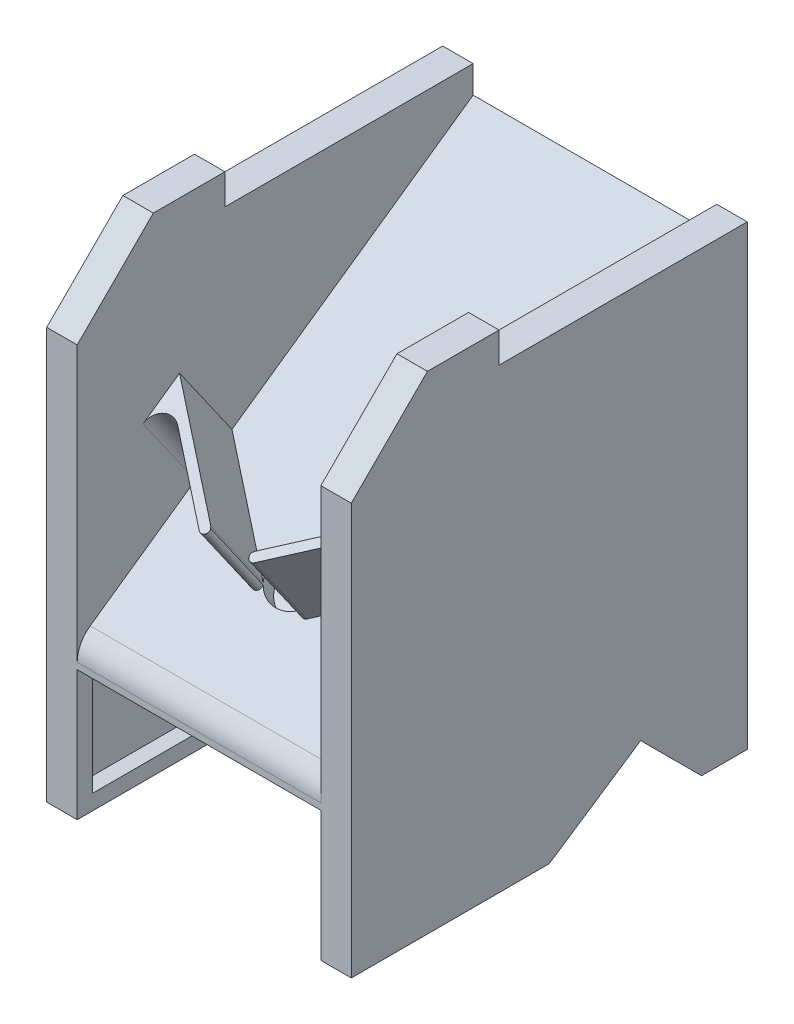
SolidWorks part; units mm, degrees
ref_plane "Front Plane" through (0, 0, 0) normal (0, 0, 1) x (1, 0, 0)
ref_plane "Top Plane" through (0, 0, 0) normal (0, 1, 0) x (1, 0, 0)
ref_plane "Right Plane" through (0, 0, 0) normal (1, 0, 0) x (0, 0, -1)
sketch "Sketch5" plane through (0, 0, 0) normal (0, 1, 0) x (1, 0, 0)
  line L1 (0, 0) -> (100, 0)
  line L2 (0, 0) -> (0, 130)
  line L3 (0, 130) -> (100, 130)
  line L4 (100, 0) -> (100, 130)
  dimension "D1" = 130
  dimension "D2" = 100
extrude "Boss-Extrude1" add sketch "Sketch5" along normal blind 150
sketch "Sketch7" plane through (100, 0, 0) normal (1, 0, 0) x (0, 0, -1)
  line L0 (130, 141.027) -> (0, 50)
  line L1 (115.8456, 131.116) -> (0, 50) construction
  line L2 (0, 150) -> (0, 0) construction
  line L3 (130, 133.7023) -> (0, 42.6754)
  line L4 (119.2871, 126.201) -> (3.4415, 45.0851) construction
  line L5 (130, 150) -> (130, 0) construction
  line L7 (0, 0) -> (130, 0)
  line L8 (130, 0) -> (130, 150)
  line L9 (130, 150) -> (0, 150)
  line L10 (0, 150) -> (0, 0)
  line L11 (0, 0) -> (130, 0)
  line L12 (130, 0) -> (130, 150)
  line L13 (130, 150) -> (0, 150)
  line L14 (0, 150) -> (0, 0)
  line M6 (0, 0) -> (130, 0)
  line M7 (130, 0) -> (130, 150)
  line M8 (130, 150) -> (0, 150)
  line M9 (0, 150) -> (0, 0)
  dimension "D1" = 50
  dimension "D2" = 55
  dimension "D3" = 0
  dimension "D4" = 6
extrude "Cut-Extrude1" cut sketch "Sketch7" against normal mid plane 80 from offset 50 contours L3 M7 M9 M6 | L0 M7 M8 M9 region at (100, 116.4204, -46.9015) region at (100, 48.0093, -76.182) offset against normal yes
ref_plane "Plane2" through (50, 0, 0) normal (-1, 0, 0) x (0, 0, 1)
sketch "Sketch17" plane through (0, 275.4121, -321.9218) normal (0, -0.8192, -0.5736) x (1, 0, 0)
  line L0 (90, 315.183) -> (90, 238.4945) construction
  line L1 (10, 374.2932) -> (90, 374.2932)
  line L2 (10, 374.2932) -> (10, 334.2932)
  line L3 (10, 334.2932) -> (90, 334.2932)
  line L4 (90, 374.2932) -> (90, 334.2932)
  line L6 (10, 315.183) -> (10, 238.4945) construction
  line L8 (10, 234.2932) -> (10, 392.9939) construction
  line L9 (10, 234.2932) -> (90, 234.2932) construction
  dimension "D1" = 40
  dimension "D2" = 100
extrude "Boss-Extrude3" add sketch "Sketch17" against normal blind 5 from offset 30
sketch "Sketch10" plane through (0, 33.5505, 23.4923) normal (0, 0.8192, 0.5736) x (1, 0, 0)
  line L0 (50, 28.6788) -> (50, 172.6872) construction
  line L1 (10, 28.6788) -> (90, 28.6788) construction
  line L2 (100, 86.0365) -> (100, 0) construction
  line L3 (0, 83.1783) -> (100, 83.1783)
  line L4 (0, 83.1783) -> (0, 53.1783)
  line L5 (0, 53.1783) -> (100, 53.1783)
  line L6 (100, 83.1783) -> (100, 53.1783)
  line L7 (0, 83.1783) -> (100, 53.1783) construction
  line L8 (0, 53.1783) -> (100, 83.1783) construction
  line L9 (10, 183.1783) -> (90, 183.1783) construction
  circle A0 centre (50, 68.1783) radius 8.75
  point P4 (50, 68.1783)
  dimension "D1" = 17.5
  dimension "D2" = 30
  dimension "D3" = 100
extrude "Cut-Extrude3" cut sketch "Sketch10" against normal blind 100 contours A0 region at (50, 72.656, -32.3561)
sketch "Sketch18" plane through (0, 0, 0) normal (1, 0, 0) x (0, 0, -1)
  line L0 (130, 150) -> (130, 0) construction
  line L1 (0, 150) -> (48.5, 150)
  line L2 (0, 150) -> (0, 160)
  line L3 (0, 160) -> (48.5, 160)
  line L4 (48.5, 150) -> (48.5, 160)
  dimension "D1" = 81.5
  dimension "D2" = 10
extrude "Boss-Extrude4" add sketch "Sketch18" along normal blind 10
extrude "Boss-Extrude5" add sketch "Sketch18<2>" against normal blind 10 from offset 100
sketch "Sketch18<2>" plane through (0, 0, 0) normal (1, 0, 0) x (0, 0, -1) same geometry as "Sketch18"
sketch "Sketch21" plane through (0, 0, 0) normal (1, 0, 0) x (0, 0, -1)
  line L0 (62.4242, 63.1905) -> (29.6581, 40.2475)
  line L1 (62.4242, 63.1905) -> (51.5263, 78.7544)
  line L2 (29.6581, 40.2475) -> (18.7602, 55.8114)
  line L3 (51.5263, 78.7544) -> (18.7602, 55.8114)
  line L4 (130, 133.7023) -> (0, 42.6754) construction
  line L5 (65.2921, 59.0948) -> (32.526, 36.1517)
  line L6 (65.2921, 59.0948) -> (32.526, 36.1517)
  line L7 (65.2921, 59.0948) -> (69.3071, 53.3607)
  line L8 (32.526, 36.1517) -> (36.541, 30.4177)
  line L9 (69.3071, 53.3607) -> (36.541, 30.4177)
  dimension "D1" = 90
  dimension "D3" = 7
  dimension "D2" = 5
extrude "Cut-Extrude5" cut sketch "Sketch21" along normal blind 70 contours L1 L3 L2 L0 | L9 L7 L5 L8 region at (0, 59.501, -40.5922) region at (0, 44.7562, -50.9166)
fillet "Fillet1" radius 5 2 edges at (5, 30.4177, -36.541) (5, 40.2475, -29.6581)
sketch "Sketch22" plane through (0, 0, 0) normal (-1, 0, 0) x (0, 0, 1)
  line L0 (-115, 0) -> (-95, 20)
  line L1 (-130, 0) -> (0, 0) construction
  line L3 (-95, 20) -> (-65, 0)
  line L4 (-115, 0) -> (-65, 0)
  dimension "D1" = 20
  dimension "D2" = 20
  dimension "D3" = 15
  dimension "D4" = 65
extrude "Cut-Extrude6" cut sketch "Sketch22" against normal blind 120
fillet "Fillet2" radius 10 1 edges at (50, 50, 0)
chamfer "Chamfer2" distance 25 angle 45 2 edges at (95, 160, 0) (5, 160, 0)
sketch "Sketch23" plane through (0, 33.5505, 23.4923) normal (0, 0.8192, 0.5736) x (1, 0, 0)
  line L0 (-11.5431, 68.1783) -> (122.3966, 68.1783) construction
  line L1 (122.3966, 63.1783) -> (-12.5005, 63.1783) construction
  line L3 (50, 51.189) -> (50, 201.2531) construction
  line L4 (57.1807, 63.1783) -> (90, 90.7169)
  line L6 (90, 187.3795) -> (90, 33.8845) construction
  line L7 (42.8193, 63.1783) -> (10, 90.7169)
  line L8 (40.8909, 60.8801) -> (8.0716, 88.4188)
  line L9 (59.1091, 60.8801) -> (91.9284, 88.4188)
  line L10 (10, 90.7169) -> (10, 70.6222)
  line L11 (10, 187.3795) -> (10, 33.8845) construction
  line L12 (90, 90.7169) -> (90, 71.7501)
  arc A0 (59.1091, 60.8801) -> (57.1807, 63.1783) centre (58.1449, 62.0292) cw
  circle A1 centre (50, 68.1783) radius 8.75 construction
  arc A2 (40.8909, 60.8801) -> (42.8193, 63.1783) centre (41.8551, 62.0292) ccw
  point P5 (57.1807, 63.1783)
  point P6 (42.8193, 63.1783)
  circle M9 centre (50, 68.1783) radius 8.75
  line M10 (10, 187.3795) -> (10, 33.8845)
  line M12 (90, 33.8845) -> (90, 187.3795)
  dimension "D1" = 5
  dimension "D2" = 50
  dimension "D3" = 3
  dimension "D4" = 3
extrude "Boss-Extrude6" add sketch "Sketch23" along normal blind 30 contours A0 L9 L4 M12 M9 | L8 A2 L7 M9 M10 region at (73.6181, 76.5869, -37.97) region at (26.3819, 76.5869, -37.97)
fillet "Fillet3" radius 5 2 edges at (10, 95.6246, -39.007) (90, 95.6246, -39.007)
sketch "Sketch24" plane through (10, 0, 0) normal (1, 0, 0) x (0, 0, -1)
  line L0 (26.7902, 44.3432) -> (29.6581, 40.2475)
  line L1 (22.6945, 41.4754) -> (17.5323, 48.8477)
  line L2 (17.5323, 48.8477) -> (5, 40.0725)
  line L3 (5, 40.0725) -> (5, 5)
  line L4 (5, 5) -> (63.4861, 5)
  line L5 (63.4861, 5) -> (95.6371, 26.434)
  line L6 (95.6371, 26.434) -> (117.0711, 5)
  line L7 (117.0711, 5) -> (125, 5)
  line L8 (125, 5) -> (125, 124.0974)
  line L9 (125, 124.0974) -> (58.4899, 77.5265)
  line L10 (58.4899, 77.5265) -> (66.52, 66.0584)
  line L11 (66.52, 66.0584) -> (69.3878, 61.9627)
  line L12 (69.3878, 61.9627) -> (76.2708, 52.1328)
  line L13 (76.2708, 52.1328) -> (43.5047, 29.1898)
  line L14 (29.5774, 31.6455) -> (28.4302, 33.2838)
  line L15 (28.4302, 33.2838) -> (25.5624, 37.3796)
  line L16 (95, 20) -> (115, 0)
  line L17 (115, 0) -> (130, 0)
  line L18 (130, 0) -> (130, 133.7023)
  line L19 (130, 133.7023) -> (51.5263, 78.7544)
  line L20 (51.5263, 78.7544) -> (62.4242, 63.1905)
  line L21 (62.4242, 63.1905) -> (65.2921, 59.0948)
  line L22 (65.2921, 59.0948) -> (69.3071, 53.3607)
  line L23 (69.3071, 53.3607) -> (40.6368, 33.2855)
  line L24 (33.6732, 34.5134) -> (32.526, 36.1517)
  line L25 (32.526, 36.1517) -> (29.6581, 40.2475)
  line L26 (29.6581, 40.2475) -> (33.7539, 43.1154)
  line L27 (26.7902, 44.3432) -> (18.7602, 55.8114)
  line L28 (18.7602, 55.8114) -> (0, 42.6754)
  line L29 (0, 42.6754) -> (0, 0)
  line L30 (0, 0) -> (65, 0)
  line L31 (65, 0) -> (95, 20)
  line L32 (95, 20) -> (115, 0)
  line L33 (115, 0) -> (130, 0)
  line L34 (130, 0) -> (130, 133.7023)
  line L35 (130, 133.7023) -> (51.5263, 78.7544)
  line L36 (51.5263, 78.7544) -> (62.4242, 63.1905)
  line L37 (62.4242, 63.1905) -> (65.2921, 59.0948)
  line L38 (65.2921, 59.0948) -> (69.3071, 53.3607)
  line L39 (69.3071, 53.3607) -> (40.6368, 33.2855)
  line L40 (33.6732, 34.5134) -> (32.526, 36.1517)
  line L41 (32.526, 36.1517) -> (29.6581, 40.2475)
  line L42 (29.6581, 40.2475) -> (33.7539, 43.1154)
  line L43 (26.7902, 44.3432) -> (18.7602, 55.8114)
  line L44 (18.7602, 55.8114) -> (0, 42.6754)
  line L45 (0, 42.6754) -> (0, 0)
  line L46 (0, 0) -> (65, 0)
  line L47 (65, 0) -> (95, 20)
  line L48 (22.6945, 41.4754) -> (25.5624, 37.3796)
  arc A0 (29.5774, 31.6455) -> (43.5047, 29.1898) centre (37.7689, 37.3813) ccw
  arc A2 (33.6732, 34.5134) -> (40.6368, 33.2855) centre (37.7689, 37.3813) ccw
  arc A3 (26.7902, 44.3432) -> (33.7539, 43.1154) centre (30.886, 47.2111) ccw
  arc A4 (33.6732, 34.5134) -> (40.6368, 33.2855) centre (37.7689, 37.3813) ccw
  arc A5 (26.7902, 44.3432) -> (33.7539, 43.1154) centre (30.886, 47.2111) ccw
  dimension "D1" = 0
  dimension "D2" = 5
extrude "Cut-Extrude7" cut sketch "Sketch24" against normal blind 5 contours A0 L14 L15 L48 L1 L2 L3 L4 L5 L6 L7 L8 L9 L10 L11 L12 L13 region at (10, 49.4465, -80.7701)
ref_plane "Plane3" through (50, 0, 0) normal (-1, 0, 0) x (0, 0, 1)
mirror "Mirror1" about plane through (50, 0, 0) normal (-1, 0, 0) of "Cut-Extrude7"
